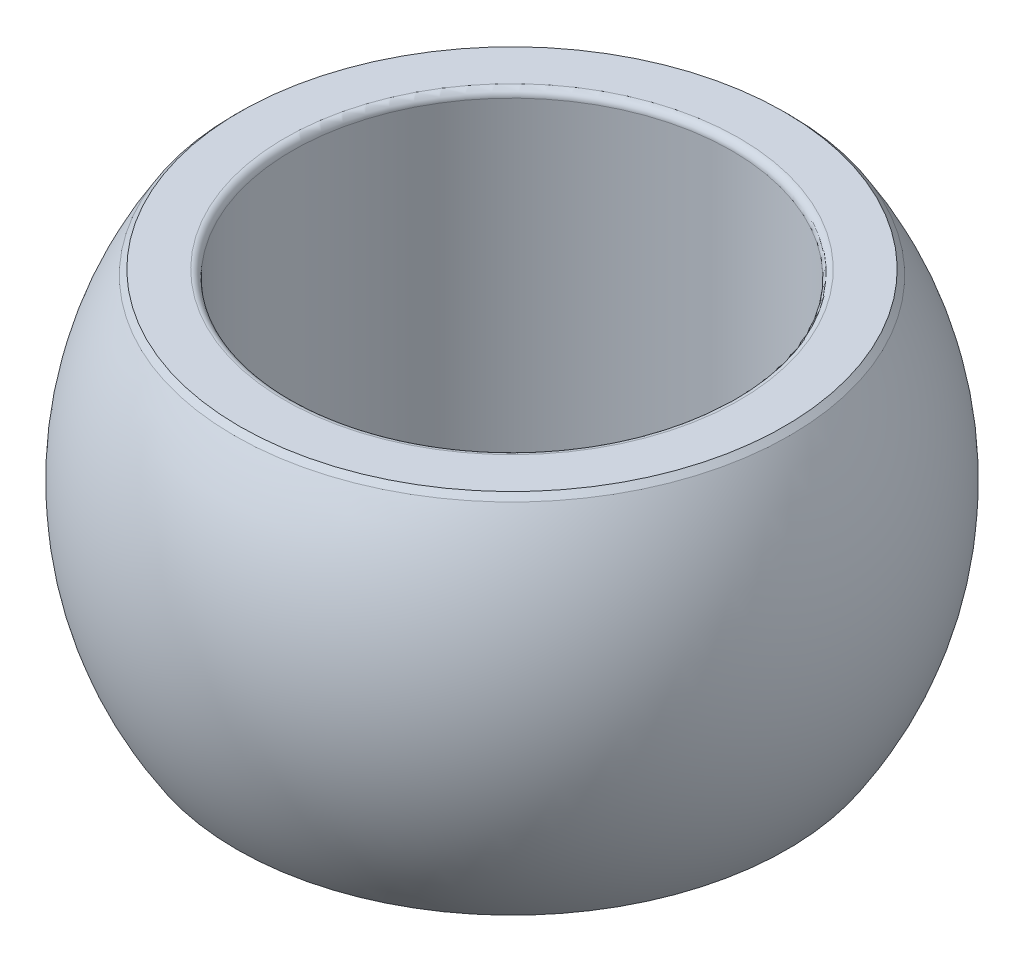
SolidWorks part; units mm, degrees
material "AISI 4340 Steel, annealed"
ref_plane "Front Plane" through (0, 0, 0) normal (0, 0, 1) x (1, 0, 0)
ref_plane "Top Plane" through (0, 0, 0) normal (0, 1, 0) x (1, 0, 0)
ref_plane "Right Plane" through (0, 0, 0) normal (1, 0, 0) x (0, 0, -1)
sketch "Sketch1" plane through (0, 0, 0) normal (0, 0, 1) x (1, 0, 0)
  line L0 (0, 0) -> (0, 5) construction
  line L1 (-6, -5) -> (-6, 5)
  line L2 (-6, 5) -> (-7.4833, 5)
  line L3 (-9, 0) -> (-6, 0) construction
  line L4 (-6, -5) -> (-7.4833, -5)
  arc A0 (-7.4833, 5) -> (-7.4833, -5) centre (0, 0) ccw
  point P9 (-6.7417, 5)
  dimension "D1" = 6
  dimension "D2" = 9
  dimension "D3" = 5
revolve "Revolve1" add sketch "Sketch1" angle 360 about L0
fillet "Fillet1" radius 0.2 2 edges at (0, -5, -6) (0, 5, -6)
chamfer "Chamfer1" distance 0.05 angle 45 2 edges at (0, 5, -7.4833) (0, -5, -7.4833) first distance on face at (0, 5, -6.2) first distance on face at (0, -5, -7.4833)
